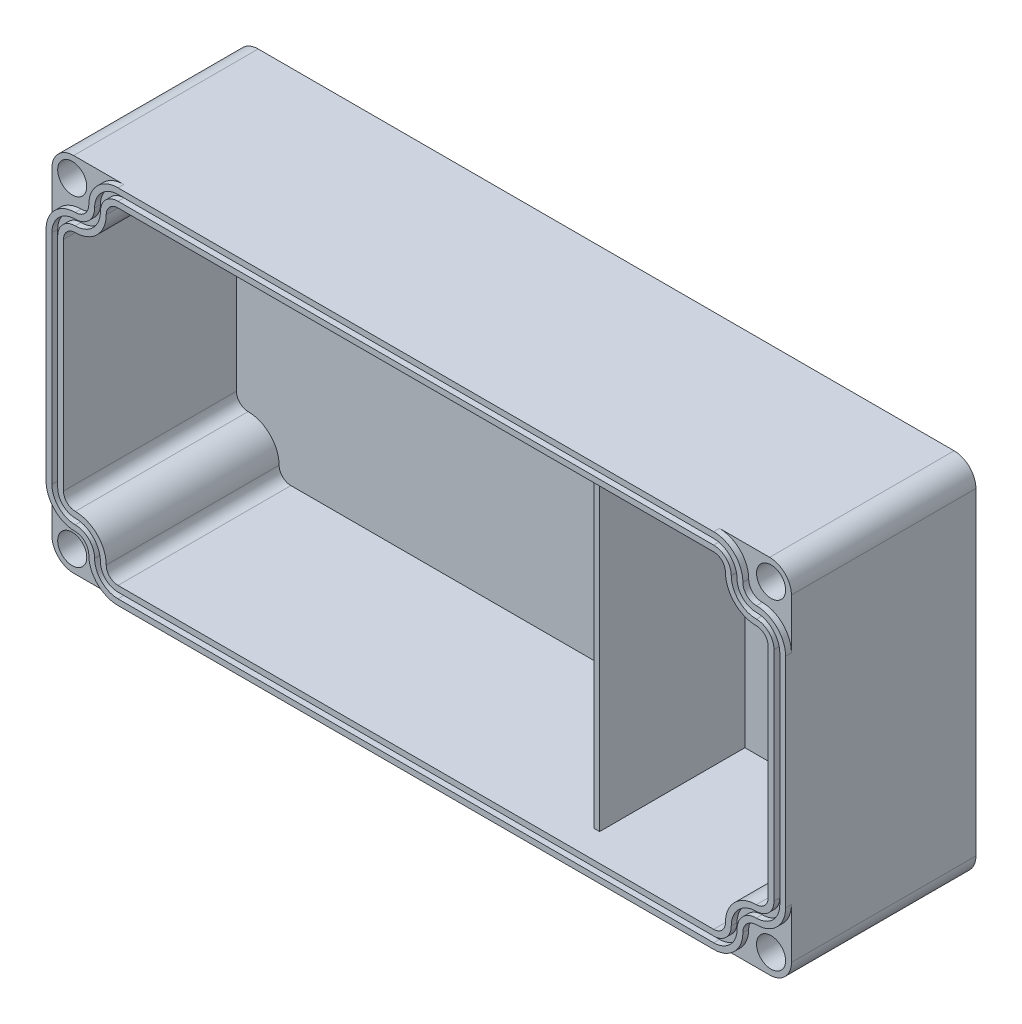
SolidWorks part; units mm, degrees
ref_plane "Plan de face" through (0, 0, 0) normal (0, 0, 1) x (1, 0, 0)
ref_plane "Plan de dessus" through (0, 0, 0) normal (0, 1, 0) x (1, 0, 0)
ref_plane "Plan de droite" through (0, 0, 0) normal (1, 0, 0) x (0, 0, -1)
sketch "Esquisse1" plane through (0, 0, 0) normal (0, 0, 1) x (1, 0, 0)
  line L1 (-48.5, 22.5) -> (48.5, 22.5)
  line L2 (-48.5, 22.5) -> (-48.5, -22.5)
  line L3 (-48.5, -22.5) -> (48.5, -22.5)
  line L4 (48.5, 22.5) -> (48.5, -22.5)
  line L5 (-48.5, 22.5) -> (48.5, -22.5) construction
  line L6 (-48.5, -22.5) -> (48.5, 22.5) construction
  point P0 (0, 0)
  dimension "D1" = 97
  dimension "D2" = 45
extrude "Boss.-Extru.1" add sketch "Esquisse1" along normal blind 23
shell "Coque1" thickness 2.4 removed face at (0, 0, 23) outward yes
ref_plane "Plan1" through (0, 0, 20) normal (0, 0, 1) x (1, 0, 0)
sketch "Esquisse8" plane through (0, 0, 20) normal (0, 0, 1) x (1, 0, 0)
  line L0 (21.5, 16.8946) -> (21.5, -12.3256)
  line L1 (48.5, -22.5) -> (48.5, 22.5) construction
  dimension "D1" = 27
rib "Nervure18" sketch "Esquisse8" sketch "Esquisse8" thickness 0.8 extrusion direction normal to sketch draft on no parameters "D1"=0.8
sketch "Esquisse10" plane through (0, 0, 0) normal (0, 0, 1) x (1, 0, 0)
  line L0 (-48.5, 22.5) -> (-48.5, 15)
  line L1 (-48.5, 22.5) -> (-48.5, -22.5) construction
  line L2 (20.7, 22.5) -> (-48.5, 22.5) construction
  line L3 (-41, 22.5) -> (-48.5, 22.5)
  line L4 (-46.88, 15) -> (-48.5, 15) construction
  line L5 (-46.88, 15) -> (-46.88, 16.62) construction
  line L6 (-41, 20.88) -> (-42.62, 20.88) construction
  line L7 (-41, 20.88) -> (-41, 22.5) construction
  arc A1 (-48.5, 15) -> (-46.88, 16.62) centre (-46.88, 15) cw
  arc A2 (-46.88, 16.62) -> (-42.62, 20.88) centre (-46.88, 20.88) ccw
  arc A3 (-42.62, 20.88) -> (-41, 22.5) centre (-41, 20.88) cw
  dimension "D1" = 7.5
extrude "Boss.-Extru.2" add sketch "Esquisse10" along normal up to surface (23 mm away) up to face at (0, 0, 23)
mirror "Symétrie1" about plane through (0, 0, 0) normal (1, 0, 0) of "Boss.-Extru.2"
mirror "Symétrie2" about plane through (0, 0, 0) normal (0, 1, 0) of "Boss.-Extru.2"
mirror "Symétrie3" about plane through (0, 0, 0) normal (0, 1, 0) of "Symétrie1"
sketch "Esquisse13" plane through (0, 0, 23) normal (0, 0, 1) x (1, 0, 0)
  line L0 (-48.1, 22.1) -> (-48.1, 24.1) construction
  line L1 (50.9, 24.9) -> (-50.9, 24.9) construction
  line L2 (-48.1, 22.1) -> (-50.1, 22.1) construction
  line L4 (-50.9, 24.9) -> (-50.9, -24.9) construction
  circle A0 centre (-48.1, 22.1) radius 2
  circle A1 centre (-48.1, 22.1) radius 2.75 construction
  dimension "D1" = 4
  dimension "D4" = 5.5
  dimension "D2" = 0.8
  dimension "D3" = 0.8
extrude "Insert" cut sketch "Esquisse13" against normal blind 5.7
mirror "Symétrie4" about plane through (0, 0, 0) normal (1, 0, 0) of "Insert"
mirror "Symétrie5" about plane through (0, 0, 0) normal (0, 1, 0) of "Symétrie4"
sketch "Esquisse14" plane through (0, 0, 23) normal (0, 0, 1) x (1, 0, 0)
  line L0 (-41, 22.5) -> (41, 22.5)
  line L1 (48.5, 15) -> (48.5, -15)
  line L2 (41, -22.5) -> (-41, -22.5)
  line L3 (-48.5, -15) -> (-48.5, 15)
  line L4 (-50.1, -15) -> (-50.1, 15)
  line L5 (-41, 24.1) -> (41, 24.1)
  line L6 (50.1, 15) -> (50.1, -15)
  line L7 (41, -24.1) -> (-41, -24.1)
  arc A0 (41, 22.5) -> (42.62, 20.88) centre (41, 20.88) cw
  arc A1 (42.62, 20.88) -> (46.88, 16.62) centre (46.88, 20.88) ccw
  arc A2 (46.88, 16.62) -> (48.5, 15) centre (46.88, 15) cw
  arc A3 (48.5, -15) -> (46.88, -16.62) centre (46.88, -15) cw
  arc A4 (46.88, -16.62) -> (42.62, -20.88) centre (46.88, -20.88) ccw
  arc A5 (42.62, -20.88) -> (41, -22.5) centre (41, -20.88) cw
  arc A6 (-41, -22.5) -> (-42.62, -20.88) centre (-41, -20.88) cw
  arc A7 (-42.62, -20.88) -> (-46.88, -16.62) centre (-46.88, -20.88) ccw
  arc A8 (-46.88, -16.62) -> (-48.5, -15) centre (-46.88, -15) cw
  arc A9 (-48.5, 15) -> (-46.88, 16.62) centre (-46.88, 15) cw
  arc A10 (-46.88, 16.62) -> (-42.62, 20.88) centre (-46.88, 20.88) ccw
  arc A11 (-42.62, 20.88) -> (-41, 22.5) centre (-41, 20.88) cw
  arc A12 (-50.1, 15) -> (-46.88, 18.22) centre (-46.88, 15) cw
  arc A13 (-46.88, 18.22) -> (-44.22, 20.88) centre (-46.88, 20.88) ccw
  arc A14 (-44.22, 20.88) -> (-41, 24.1) centre (-41, 20.88) cw
  arc A15 (41, 24.1) -> (44.22, 20.88) centre (41, 20.88) cw
  arc A16 (44.22, 20.88) -> (46.88, 18.22) centre (46.88, 20.88) ccw
  arc A17 (46.88, 18.22) -> (50.1, 15) centre (46.88, 15) cw
  arc A18 (50.1, -15) -> (46.88, -18.22) centre (46.88, -15) cw
  arc A19 (46.88, -18.22) -> (44.22, -20.88) centre (46.88, -20.88) ccw
  arc A20 (44.22, -20.88) -> (41, -24.1) centre (41, -20.88) cw
  arc A21 (-41, -24.1) -> (-44.22, -20.88) centre (-41, -20.88) cw
  arc A22 (-44.22, -20.88) -> (-46.88, -18.22) centre (-46.88, -20.88) ccw
  arc A23 (-46.88, -18.22) -> (-50.1, -15) centre (-46.88, -15) cw
  dimension "D1" = 1.6
extrude "Extru.-Mince1" add sketch "Esquisse14" along normal blind 0.8 thin thin type one direction wall 0.8
fillet "Congé1" radius 3 4 edges at (-50.9, -24.9, 10.3) (50.9, -24.9, 10.3) (50.9, 24.9, 10.3) (-50.9, 24.9, 10.3)
sketch "Esquisse16" plane through (0, 0, 0) normal (0, 0, 1) x (1, 0, 0)
  circle A0 centre (-31.1716, 18.1378) radius 1.5
  circle A1 centre (14.1284, 18.1378) radius 1.5
  circle A2 centre (14.1284, -17.7622) radius 1.5
  point P0 (-31.1716, 18.1378)
  dimension "D1" = 3
  dimension "D2" = 3
  dimension "D3" = 3
extrude "Boss.-Extru.3" add sketch "Esquisse16" along normal blind 6
fillet "Congé2" radius 2 3 edges at (15.6284, -17.7622, 0) (15.6284, 18.1378, 0) (-29.6716, 18.1378, 0)
sketch "Esquisse17" plane through (0, 0, 23) normal (0, 0, 1) x (1, 0, 0)
  circle A0 centre (-48.1, 22.1) radius 2.75 construction
  dimension "D1" = 5.5
equation "\"buse\"= 0.8"
equation "\"D1@Coque1\"=\"buse\"*3"
equation "\"hauteur\"=10"
equation "\"D1@Nervure1\"=\"hauteur\""
equation "\"D1@Nervure18\"=\"buse\""
equation "\"D2@Esquisse13\"=\"buse\"*1"
equation "\"D3@Esquisse13\"=1*\"buse\""
